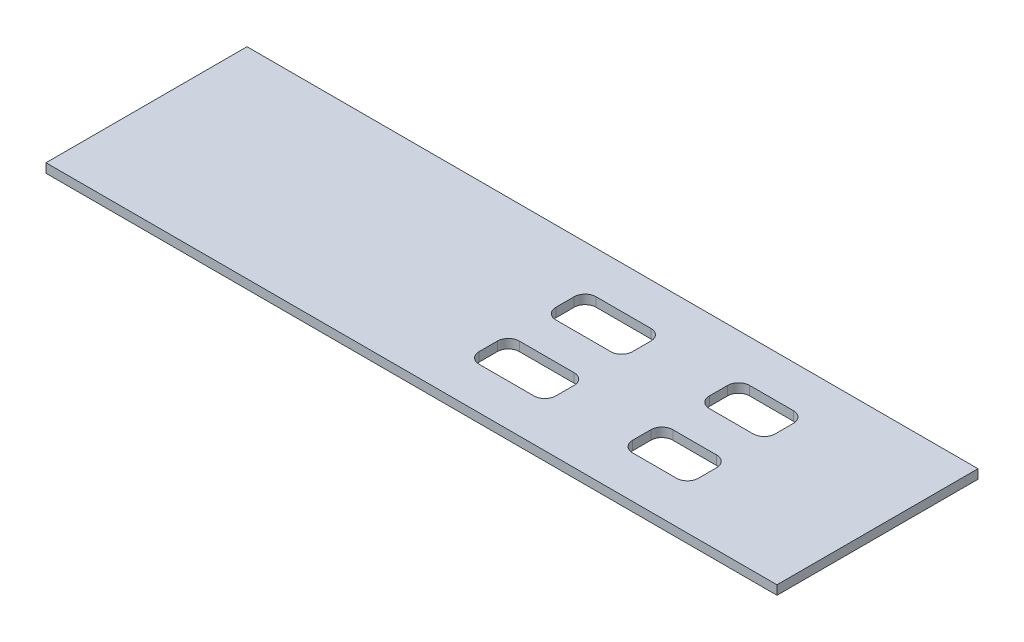
SolidWorks part; units mm, degrees
ref_plane "Front Plane" through (0, 0, 0) normal (0, 0, 1) x (1, 0, 0)
ref_plane "Top Plane" through (0, 0, 0) normal (0, 1, 0) x (1, 0, 0)
ref_plane "Right Plane" through (0, 0, 0) normal (1, 0, 0) x (0, 0, -1)
sketch "Sketch1" plane through (0, 0, 0) normal (0, 1, 0) x (1, 0, 0)
  line L1 (0, 0) -> (152.4, 0)
  line L2 (0, 0) -> (0, 69.85)
  line L3 (0, 69.85) -> (152.4, 69.85)
  line L4 (152.4, 0) -> (152.4, 69.85)
  dimension "D1" = 69.85
  dimension "D2" = 152.4
extrude "Boss-Extrude1" add sketch "Sketch1" along normal blind 3.175
sketch "Sketch2" plane through (0, 3.175, 0) normal (0, 1, 0) x (1, 0, 0)
  line L0 (0, 69.85) -> (0, 0) construction
  line L1 (30.48, 55.245) -> (57.15, 55.245)
  line L2 (30.48, 55.245) -> (30.48, 41.275)
  line L3 (30.48, 41.275) -> (57.15, 41.275)
  line L4 (57.15, 55.245) -> (57.15, 41.275)
  line L5 (83.82, 55.245) -> (106.68, 55.245)
  line L6 (83.82, 55.245) -> (83.82, 41.275)
  line L7 (83.82, 41.275) -> (106.68, 41.275)
  line L8 (106.68, 55.245) -> (106.68, 41.275)
  line L9 (152.4, 0) -> (152.4, 69.85) construction
  line L10 (30.48, 28.575) -> (57.15, 28.575)
  line L11 (30.48, 28.575) -> (30.48, 14.605)
  line L12 (30.48, 14.605) -> (57.15, 14.605)
  line L13 (57.15, 28.575) -> (57.15, 14.605)
  line L14 (83.82, 28.575) -> (106.68, 28.575)
  line L15 (83.82, 28.575) -> (83.82, 14.605)
  line L16 (83.82, 14.605) -> (106.68, 14.605)
  line L17 (106.68, 28.575) -> (106.68, 14.605)
  point P10 (83.82, 48.26)
  point P17 (0, 34.925)
  point P22 (0, 0)
  point P25 (29.21, 34.925)
  point P26 (0, 0)
  point P27 (16.4499, 34.925)
  dimension "D1" = 26.67
  dimension "D2" = 22.86
  dimension "D3" = 45.72
  dimension "D4" = 13.97
  dimension "D5" = 12.7
  dimension "D6" = 6.35
  dimension "D7" = 30.48
extrude "Cut-Extrude1" cut sketch "Sketch2" against normal through all
fillet "Fillet1" radius 3.81 16 edges at (83.82, 1.5875, -14.605) (83.82, 1.5875, -41.275) (30.48, 1.5875, -41.275) (30.48, 1.5875, -14.605) (106.68, 1.5875, -14.605) (57.15, 1.5875, -41.275) (57.15, 1.5875, -14.605) (106.68, 1.5875, -41.275) (106.68, 1.5875, -28.575) (106.68, 1.5875, -55.245) (57.15, 1.5875, -28.575) (57.15, 1.5875, -55.245) (30.48, 1.5875, -28.575) (83.82, 1.5875, -28.575) (83.82, 1.5875, -55.245) (30.48, 1.5875, -55.245)
sketch "Sketch4" plane through (0, 0, 0) normal (-1, 0, 0) x (0, 0, 1)
  line L1 (-69.85, 3.175) -> (0, 3.175)
  line L2 (-69.85, 3.175) -> (-69.85, 0)
  line L3 (-69.85, 0) -> (0, 0)
  line L4 (0, 3.175) -> (0, 0)
extrude "Boss-Extrude2" add sketch "Sketch4" along normal blind 101.6
